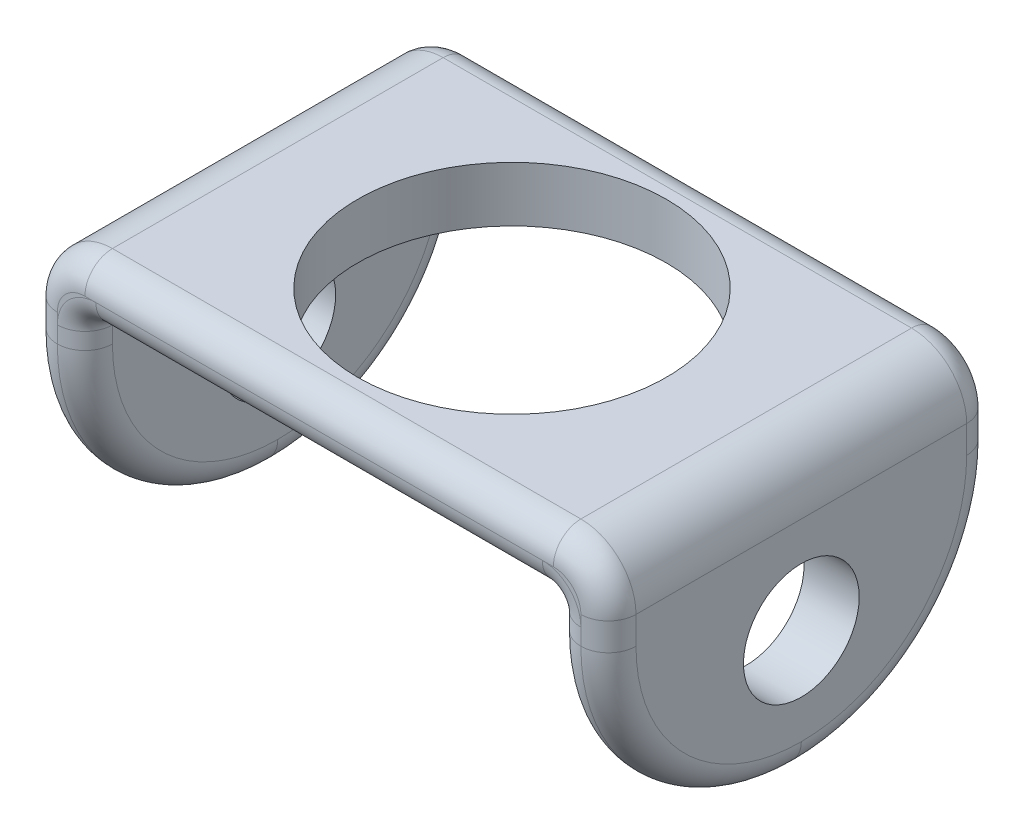
SolidWorks part; units mm, degrees
ref_plane "Front Plane" through (0, 0, 0) normal (0, 0, 1) x (1, 0, 0)
ref_plane "Top Plane" through (0, 0, 0) normal (0, 1, 0) x (1, 0, 0)
ref_plane "Right Plane" through (0, 0, 0) normal (1, 0, 0) x (0, 0, -1)
sketch "Sketch1" plane through (0, 0, 0) normal (0, 1, 0) x (1, 0, 0)
  line L1 (52.5, 35) -> (52.5, -35)
  line L2 (52.5, -35) -> (-52.5, -35)
  line L3 (-52.5, -35) -> (-52.5, 35)
  line L4 (-52.5, 35) -> (52.5, 35)
  circle A0 centre (0, 0) radius 22.5 construction
  circle A1 centre (0, 0) radius 28
  point P11 (0, -35)
  point P13 (-52.5, 0)
  dimension "D1" = 45
  dimension "D2" = 56
  dimension "D3" = 105
  dimension "D4" = 70
extrude "Boss-Extrude1" add sketch "Sketch1" along normal blind 10
sketch "Sketch3" plane through (0, 0, 0) normal (0, -1, 0) x (1, 0, 0)
  line L0 (52.5, -35) -> (-52.5, -35) construction
  line L1 (-52.5, 35) -> (-42.5, 35)
  line L2 (-52.5, 35) -> (-52.5, -35)
  line L3 (-52.5, -35) -> (-42.5, -35)
  line L4 (-42.5, 35) -> (-42.5, -35)
  line L5 (42.5, 35) -> (52.5, 35)
  line L7 (52.5, 35) -> (52.5, -35)
  line L8 (52.5, -35) -> (42.5, -35)
  line L9 (42.5, 35) -> (42.5, -35)
  dimension "D1" = 85
  dimension "D2" = 10
extrude "Boss-Extrude2" add sketch "Sketch3" along normal blind 40
sketch "Sketch5" plane through (52.5, 0, 0) normal (1, 0, 0) x (0, 0, -1)
  line L0 (-35, 10) -> (35, 10) construction
  circle A0 centre (0, -17.5) radius 10.5
  dimension "D2" = 21
  dimension "D1" = 27.5
extrude "Cut-Extrude1" cut sketch "Sketch5" against normal through all
fillet "Fillet1" radius 35 4 edges at (47.5, -40, 35) (47.5, -40, -35) (-47.5, -40, 35) (-47.5, -40, -35)
fillet "Fillet2" radius 10 2 edges at (-52.5, 10, 0) (52.5, 10, 0)
fillet "Fillet3" radius 2 2 edges at (42.5, 0, 0) (-42.5, 0, 0)
fillet "Fillet4" radius 5 28 edges at (-41.9142, -0.5858, 35) (-42.5, -29.7487, 24.7487) (-42.5, -29.7487, -24.7487) (-41.9142, -0.5858, -35) (0, 0, -35) (41.9142, -0.5858, -35) (42.5, -29.7487, -24.7487) (42.5, -29.7487, 24.7487) (41.9142, -0.5858, 35) (-49.5711, 7.0711, 35) (-52.5, -2.5, 35) (-52.5, -29.7487, 24.7487) (-52.5, -29.7487, -24.7487) (-52.5, -2.5, -35) (-49.5711, 7.0711, -35) (0, 10, -35) (49.5711, 7.0711, -35) (52.5, -2.5, -35) (52.5, -29.7487, -24.7487) (52.5, -29.7487, 24.7487) (52.5, -2.5, 35) (49.5711, 7.0711, 35) (0, 0, 35) (0, 10, 35) (-42.5, -3.5, 35) (-42.5, -3.5, -35) (42.5, -3.5, -35) (42.5, -3.5, 35)
